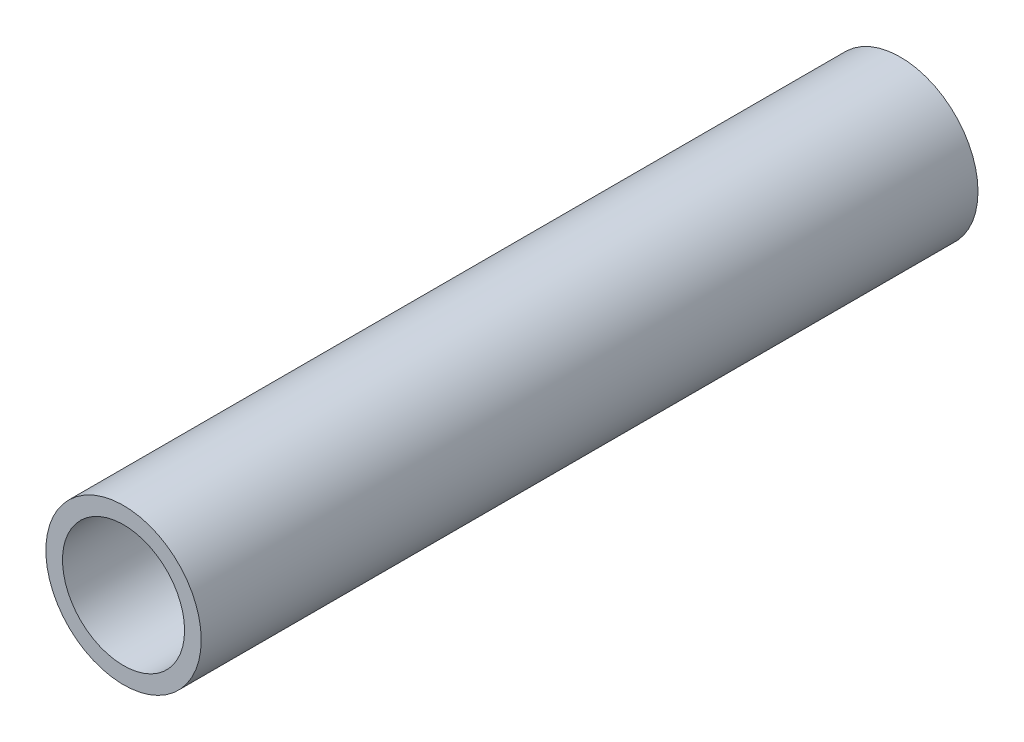
SolidWorks part; units mm, degrees
ref_plane "Front Plane" through (0, 0, 0) normal (0, 0, 1) x (1, 0, 0)
ref_plane "Top Plane" through (0, 0, 0) normal (0, 1, 0) x (1, 0, 0)
ref_plane "Right Plane" through (0, 0, 0) normal (1, 0, 0) x (0, 0, -1)
sketch "Sketch1" plane through (0, 0, 0) normal (0, 0, 1) x (1, 0, 0)
  circle A0 centre (0, 0) radius 2.75
  circle A1 centre (0, 0) radius 3.5
  dimension "D1" = 5.5
  dimension "D2" = 7
extrude "Boss-Extrude1" add sketch "Sketch1" along normal blind 35
